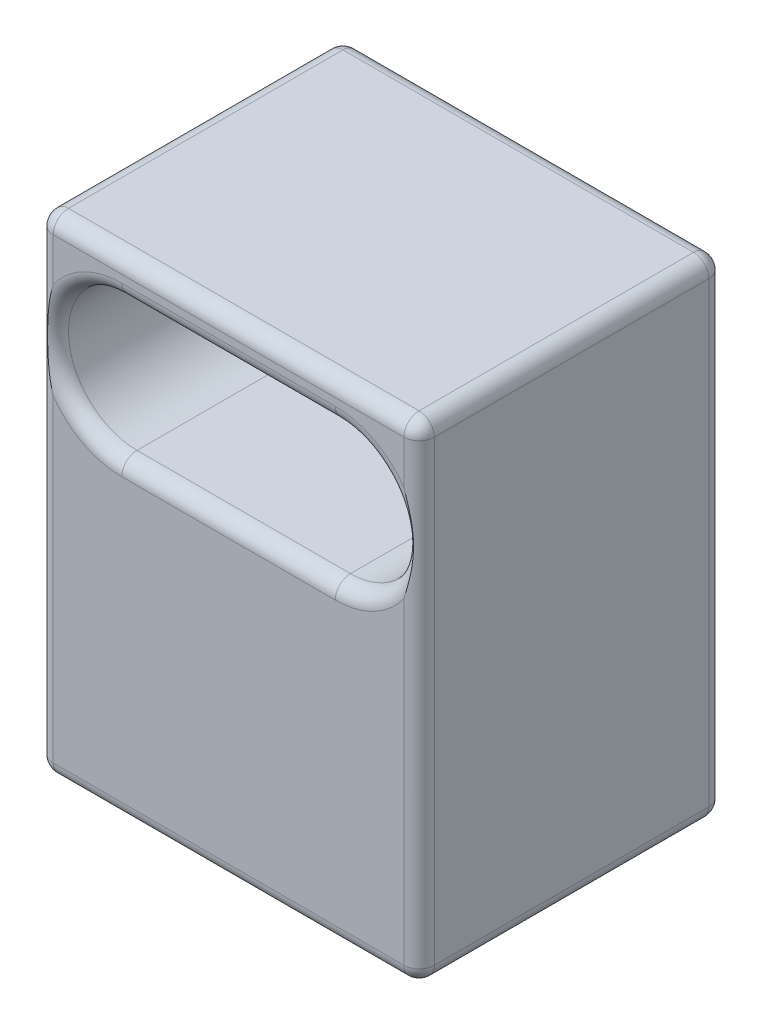
SolidWorks part; units mm, degrees
material "PLA"
ref_plane "Alzado" through (0, 0, 0) normal (0, 0, 1) x (1, 0, 0)
ref_plane "Planta" through (0, 0, 0) normal (0, 1, 0) x (1, 0, 0)
ref_plane "Vista lateral" through (0, 0, 0) normal (1, 0, 0) x (0, 0, -1)
sketch "Croquis1" plane through (0, 0, 0) normal (0, 0, 1) x (1, 0, 0)
  line L1 (12.5, 16) -> (-12.5, 16)
  line L2 (12.5, 16) -> (12.5, -16)
  line L3 (12.5, -16) -> (-12.5, -16)
  line L4 (-12.5, 16) -> (-12.5, -16)
  line L5 (12.5, 16) -> (-12.5, -16) construction
  line L6 (12.5, -16) -> (-12.5, 16) construction
  point P0 (0, 0)
  dimension "D1" = 32
  dimension "D2" = 25
extrude "Saliente-Extruir1" add sketch "Croquis1" along normal blind 20
sketch "Croquis7" plane through (0, 0, 20) normal (0, 0, 1) x (1, 0, 0)
  line L0 (-12.5, 9) -> (12.5, 9) construction
  line L1 (-12.5, 16) -> (-12.5, -16) construction
  line L2 (12.5, -16) -> (12.5, 16) construction
  line L3 (12.5, 16) -> (-12.5, 16) construction
  line L4 (-5, 9) -> (5, 9) construction
  line L5 (-5, 11.75) -> (5, 11.75)
  line L6 (-5, 6.25) -> (5, 6.25)
  arc A0 (-5, 11.75) -> (-5, 6.25) centre (-5, 9) ccw
  arc A1 (5, 6.25) -> (5, 11.75) centre (5, 9) ccw
  point P10 (0, 9)
  dimension "D1" = 7
  dimension "D2" = 7.5
  dimension "D3" = 5
  dimension "D4" = 5.5
extrude "Cortar-Extruir2" cut sketch "Croquis7" against normal blind 20
sketch "Croquis8" plane through (0, 0, 20) normal (0, 0, 1) x (1, 0, 0)
  line L0 (-12.5, 9) -> (12.5, 9) construction
  line L1 (-12.5, 16) -> (-12.5, -16) construction
  line L2 (12.5, -16) -> (12.5, 16) construction
  line L3 (12.5, 16) -> (-12.5, 16) construction
  line L4 (-7, 9) -> (7, 9) construction
  line L5 (-7, 13.5) -> (7, 13.5)
  line L6 (-7, 4.5) -> (7, 4.5)
  arc A0 (-7, 13.5) -> (-7, 4.5) centre (-7, 9) ccw
  arc A1 (7, 4.5) -> (7, 13.5) centre (7, 9) ccw
  point P10 (0, 9)
  dimension "D1" = 7
  dimension "D2" = 9
  dimension "D3" = 7
  dimension "D4" = 12.5
extrude "Cortar-Extruir3" cut sketch "Croquis8" against normal blind 10
sketch "Croquis9" plane through (0, -16, 0) normal (0, -1, 0) x (1, 0, 0)
  line L0 (0, 0) -> (0, 20) construction
  line L1 (-12.5, 20) -> (12.5, 20) construction
  line L2 (-12.5, 0) -> (12.5, 0) construction
  circle A0 centre (0, 12.5) radius 2.5
  dimension "D2" = 5
  dimension "D1" = 12.5
extrude "Cortar-Extruir4" cut sketch "Croquis9" against normal blind 10
sketch "Croquis10" plane through (0, 0, 0) normal (0, 0, -1) x (-1, 0, 0)
  line L0 (-12.5, -9) -> (12.5, -9) construction
  line L1 (-12.5, -16) -> (-12.5, 16) construction
  line L2 (12.5, 16) -> (12.5, -16) construction
  line L3 (12.5, -16) -> (-12.5, -16) construction
  line L5 (4, -7) -> (-4, -7)
  line L6 (4, -7) -> (4, -11)
  line L7 (4, -11) -> (-4, -11)
  line L8 (-4, -7) -> (-4, -11)
  line L9 (4, -7) -> (-4, -11) construction
  line L10 (4, -11) -> (-4, -7) construction
  point P8 (0, -9)
  dimension "D1" = 7
  dimension "D2" = 4
  dimension "D3" = 8
extrude "Cortar-Extruir5" cut sketch "Croquis10" against normal blind 17
fillet "Redondeo1" radius 1 21 edges at (7.75, 9, 10) (0, 11.75, 10) (-7.75, 9, 10) (0, 16, 0) (0, -16, 0) (0, -16, 10) (12.5, -16, 10) (12.5, 16, 10) (12.5, 0, 0) (-12.5, 16, 10) (-12.5, -16, 10) (-12.5, 0, 0) (0, 16, 20) (12.5, 0, 20) (0, -16, 20) (-12.5, 0, 20) (11.5, 9, 20) (0, 13.5, 20) (-11.5, 9, 20) (0, 4.5, 20) (0, 6.25, 10)
